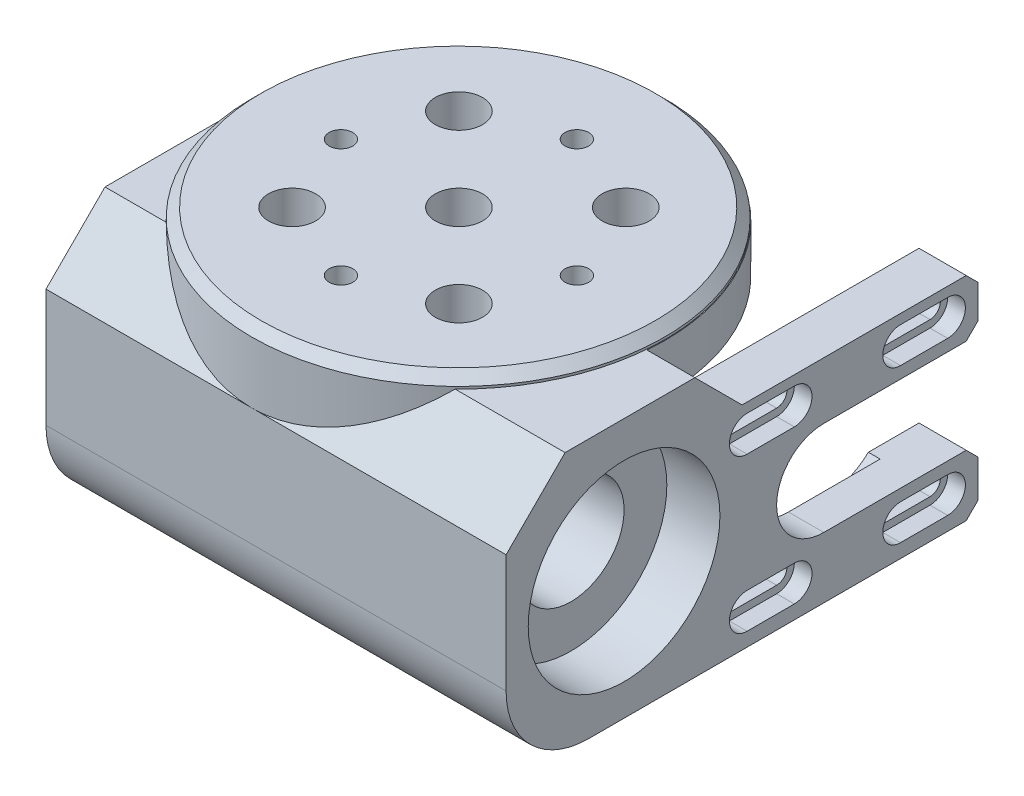
SolidWorks part; units mm, degrees
material "PLA Generic"
ref_plane "Front Plane" through (0, 0, 0) normal (0, 0, 1) x (1, 0, 0)
ref_plane "Top Plane" through (0, 0, 0) normal (0, 1, 0) x (1, 0, 0)
ref_plane "Right Plane" through (0, 0, 0) normal (1, 0, 0) x (0, 0, -1)
sketch "Sketch1" plane through (0, 0, 0) normal (0, 1, 0) x (1, 0, 0)
  circle A0 centre (0, 0) radius 4
  circle A1 centre (-0.1257, 0) radius 35
  dimension "D1" = 8
  dimension "D2" = 70
extrude "Boss-Extrude1" add sketch "Sketch1" along normal blind 2
chamfer "Chamfer1" distance 1.6 angle 45 1 edges at (-0.1257, 2, 35)
sketch "Sketch2" plane through (0, 0, 0) normal (0, -1, 0) x (1, 0, 0)
  line L3 (-35, 0) -> (-35, 35)
  line L4 (-35, 35) -> (35, 35)
  line L5 (35, 35) -> (35, 0)
  circle A2 centre (0, 0) radius 4
  arc A3 (-35, 0) -> (35, 0) centre (0, 0) ccw
  dimension "D1" = 70
  dimension "D2" = 8
extrude "Boss-Extrude2" add sketch "Sketch2" along normal blind 8
sketch "Sketch3" plane through (0, -8, 0) normal (0, -1, 0) x (1, 0, 0)
  line L0 (-35, 0) -> (-35, 35)
  line L1 (11.619, -3) -> (27, -3)
  line L2 (35, 35) -> (35, -45)
  line L3 (-35, 35) -> (35, 35)
  line L4 (-34.641, -5) -> (-10.9087, -5)
  line L5 (35, -45) -> (27, -45)
  line L6 (27, -45) -> (27, -3)
  circle A0 centre (0, 0) radius 4
  arc A1 (-10.9087, -5) -> (11.619, -3) centre (0, 0) ccw
  arc A2 (-35, 0) -> (-34.641, -5) centre (0, 0) ccw
  dimension "D1" = 12
  dimension "D2" = 40
  dimension "D3" = 8
  dimension "D4" = 80
  dimension "D5" = 38
extrude "Boss-Extrude3" add sketch "Sketch3" along normal blind 36
sketch "Sketch4" plane through (35, 0, 0) normal (1, 0, 0) x (0, 0, -1)
  line L6 (0, 0) -> (-35, 0)
  line L7 (-35, 0) -> (-35, -44)
  line L8 (-35, -44) -> (45, -44)
  line L9 (45, -44) -> (45, -8)
  line L10 (45, -8) -> (0, -8)
  line L11 (0, -8) -> (0, 0)
  line L12 (0, 0) -> (-35, 0)
  line L13 (-35, 0) -> (-35, -44)
  line L14 (-35, -44) -> (45, -44)
  line L15 (45, -44) -> (45, -8)
  line L16 (45, -8) -> (0, -8)
  line L17 (0, -8) -> (0, 0)
  dimension "D1" = 0
extrude "Boss-Extrude4" add sketch "Sketch4" along normal blind 8
sketch "Sketch5" plane through (27, 0, 0) normal (-1, 0, 0) x (0, 0, 1)
  line L5 (-3, -8) -> (-22.2711, -8)
  line L6 (-22.2711, -8) -> (-45, -8)
  line L7 (-45, -8) -> (-45, -44)
  line L8 (-45, -44) -> (-3, -44)
  line L9 (-3, -44) -> (-3, -8)
  line L10 (-3, -8) -> (-22.2711, -8)
  line L11 (-22.2711, -8) -> (-45, -8)
  line L12 (-45, -8) -> (-45, -44)
  line L13 (-45, -44) -> (-3, -44)
  line L14 (-3, -44) -> (-3, -8)
  dimension "D1" = 0
extrude "Cut-Extrude1" cut sketch "Sketch5" against normal blind 8
sketch "Sketch6" plane through (-35, 0, 0) normal (-1, 0, 0) x (0, 0, 1)
  line L0 (35, -44) -> (35, 0) construction
  line L1 (33.4, 2) -> (-33.4, 2) construction
  circle A0 centre (15, -22.4) radius 9
  dimension "D1" = 20
  dimension "D2" = 24.4
  dimension "D3" = 18
extrude "Cut-Extrude2" cut sketch "Sketch6" against normal through all
sketch "Sketch7" plane through (43, 0, 0) normal (1, 0, 0) x (0, 0, -1)
  circle A0 centre (-15, -22.4) radius 16.25
  dimension "D1" = 32.5
extrude "Cut-Extrude3" cut sketch "Sketch7" against normal blind 9
sketch "Sketch8" plane through (-35, 0, 0) normal (-1, 0, 0) x (0, 0, 1)
  circle A0 centre (15, -22.4) radius 16.25
  dimension "D1" = 32.5
extrude "Cut-Extrude4" cut sketch "Sketch8" against normal blind 9
chamfer "Chamfer2" distance 10 angle 45 2 edges at (-17.5629, 0, 35) (21.4371, 0, 35)
fillet "Fillet1" radius 14 2 edges at (4, -44, 35) (-22.7749, -44, -5)
fillet "Fillet2" radius 14 1 edges at (23.3095, -44, -3)
sketch "Sketch9" plane through (35, 0, 0) normal (-1, 0, 0) x (0, 0, 1)
  line L3 (-45, -8) -> (-45, -44) construction
  line L6 (-45, -44) -> (-45, -25.6549) construction
  line L7 (-45, -25.6549) -> (-12, -25.6549) construction
  line L8 (-12, -8) -> (-12, -44) construction
  line L11 (-45, -33.6549) -> (-45, -17.6549)
  line L12 (-22.8603, -17.6549) -> (-22.8603, -33.6549) construction
  line L13 (-45, -17.6549) -> (-18.8603, -17.6549)
  line L14 (-45, -33.6549) -> (-18.8603, -33.6549)
  arc A4 (-18.8603, -33.6549) -> (-18.8603, -17.6549) centre (-18.8603, -25.6549) ccw
  circle A5 centre (15, -22.4) radius 9 construction
  point P3 (-45, -8)
  point P13 (-22.8603, -25.6549)
  dimension "D1" = 4
  dimension "D4" = 16
  dimension "D2" = 16
  dimension "D3" = 38
extrude "Cut-Extrude5" cut sketch "Sketch9" against normal blind 9
sketch "Sketch10" plane through (35, 0, 0) normal (-1, 0, 0) x (0, 0, 1)
  line L29 (-45, -8) -> (-45, -44) construction
  line L30 (-22.8603, -12.6549) -> (-22.8603, -38.6549) construction
  line L31 (-18.8603, -17.6549) -> (-18.8603, -33.6549) construction
  line L32 (-18.8603, -33.6549) -> (-45, -17.6549) construction
  line L33 (-45, -17.6549) -> (-45, -33.6549) construction
  line L34 (-45, -33.6549) -> (-18.8603, -17.6549) construction
  line L35 (-18.8603, -17.6549) -> (-45, -17.6549) construction
  line L36 (-26.8603, -17.6549) -> (-18.8603, -33.6549) construction
  line L37 (-35.8603, -25.6549) -> (-9.8603, -25.6549) construction
  line L38 (-35.8603, -38.6549) -> (-35.8603, -12.6549) construction
  line L39 (-35.8603, -12.6549) -> (-9.8603, -12.6549) construction
  line L40 (-9.8603, -12.6549) -> (-9.8603, -38.6549) construction
  line L41 (-9.8603, -38.6549) -> (-35.8603, -38.6549) construction
  line L42 (-39.8603, -12.6549) -> (-31.8603, -12.6549) construction
  line L43 (-39.8603, -10.9049) -> (-31.8603, -10.9049)
  line L44 (-39.8603, -14.4049) -> (-31.8603, -14.4049)
  line L45 (-39.8603, -38.6549) -> (-31.8603, -38.6549) construction
  line L46 (-39.8603, -36.9049) -> (-31.8603, -36.9049)
  line L47 (-39.8603, -40.4049) -> (-31.8603, -40.4049)
  line L48 (-13.8603, -12.6549) -> (-5.8603, -12.6549) construction
  line L49 (-13.8603, -10.9049) -> (-5.8603, -10.9049)
  line L50 (-13.8603, -14.4049) -> (-5.8603, -14.4049)
  line L51 (-13.8603, -38.6549) -> (-5.8603, -38.6549) construction
  line L52 (-13.8603, -36.9049) -> (-5.8603, -36.9049)
  line L53 (-13.8603, -40.4049) -> (-5.8603, -40.4049)
  arc A8 (-39.8603, -10.9049) -> (-39.8603, -14.4049) centre (-39.8603, -12.6549) ccw
  arc A9 (-31.8603, -14.4049) -> (-31.8603, -10.9049) centre (-31.8603, -12.6549) ccw
  arc A10 (-39.8603, -36.9049) -> (-39.8603, -40.4049) centre (-39.8603, -38.6549) ccw
  arc A11 (-31.8603, -40.4049) -> (-31.8603, -36.9049) centre (-31.8603, -38.6549) ccw
  arc A12 (-13.8603, -10.9049) -> (-13.8603, -14.4049) centre (-13.8603, -12.6549) ccw
  arc A13 (-5.8603, -14.4049) -> (-5.8603, -10.9049) centre (-5.8603, -12.6549) ccw
  arc A14 (-13.8603, -36.9049) -> (-13.8603, -40.4049) centre (-13.8603, -38.6549) ccw
  arc A15 (-5.8603, -40.4049) -> (-5.8603, -36.9049) centre (-5.8603, -38.6549) ccw
  point P50 (-22.8603, -25.6549)
  point P53 (-22.8603, -25.6549)
  point P56 (-35.8603, -25.6549)
  point P60 (-35.8603, -12.6549)
  point P66 (-35.8603, -38.6549)
  point P73 (-9.8603, -12.6549)
  point P80 (-9.8603, -38.6549)
  dimension "D11" = 8
  dimension "D12" = 26
  dimension "D13" = 26
  dimension "D14" = 8
  dimension "D15" = 8
  dimension "D16" = 8
  dimension "D17" = 8
  dimension "D18" = 3.5
  dimension "D19" = 3.5
  dimension "D20" = 3.5
  dimension "D21" = 3.5
extrude "Cut-Extrude6" cut sketch "Sketch10" against normal blind 9
chamfer "Chamfer3" distance 2 angle 45 4 edges at (39, -17.6549, -45) (39, -8, -45) (39, -33.6549, -45) (39, -44, -45)
sketch "Sketch11" plane through (43, 0, 0) normal (1, 0, 0) x (0, 0, -1)
  line L0 (39.8603, -36.9049) -> (31.8603, -36.9049) construction
  line L1 (31.8603, -40.4049) -> (39.8603, -40.4049) construction
  line L2 (5.8603, -40.4049) -> (13.8603, -40.4049) construction
  line L3 (13.8603, -36.9049) -> (5.8603, -36.9049) construction
  line L4 (31.8603, -14.4049) -> (39.8603, -14.4049) construction
  line L5 (39.8603, -10.9049) -> (31.8603, -10.9049) construction
  line L6 (13.8603, -10.9049) -> (5.8603, -10.9049) construction
  line L7 (5.8603, -14.4049) -> (13.8603, -14.4049) construction
  line L8 (39.8603, -36.9049) -> (31.8603, -36.9049)
  line L9 (31.8603, -40.4049) -> (39.8603, -40.4049)
  line L10 (5.8603, -40.4049) -> (13.8603, -40.4049)
  line L11 (13.8603, -36.9049) -> (5.8603, -36.9049)
  line L12 (31.8603, -14.4049) -> (39.8603, -14.4049)
  line L13 (39.8603, -10.9049) -> (31.8603, -10.9049)
  line L14 (13.8603, -12.6549) -> (5.8603, -12.6549) construction
  line L15 (13.8603, -15.6549) -> (5.8603, -15.6549)
  line L16 (13.8603, -9.6549) -> (5.8603, -9.6549)
  line L17 (39.8603, -12.6549) -> (31.8603, -12.6549) construction
  line L18 (39.8603, -15.6549) -> (31.8603, -15.6549)
  line L19 (39.8603, -9.6549) -> (31.8603, -9.6549)
  line L20 (13.8603, -38.6549) -> (5.8603, -38.6549) construction
  line L21 (13.8603, -41.6549) -> (5.8603, -41.6549)
  line L22 (13.8603, -35.6549) -> (5.8603, -35.6549)
  line L23 (31.8603, -38.6549) -> (39.8603, -38.6549) construction
  line L24 (31.8603, -35.6549) -> (39.8603, -35.6549)
  line L25 (31.8603, -41.6549) -> (39.8603, -41.6549)
  line L42 (13.8603, -10.9049) -> (5.8603, -10.9049)
  line L43 (5.8603, -14.4049) -> (13.8603, -14.4049)
  arc A0 (39.8603, -40.4049) -> (39.8603, -36.9049) centre (39.8603, -38.6549) ccw construction
  arc A1 (31.8603, -36.9049) -> (31.8603, -40.4049) centre (31.8603, -38.6549) ccw construction
  arc A2 (13.8603, -15.6549) -> (13.8603, -9.6549) centre (13.8603, -12.6549) ccw
  arc A3 (5.8603, -9.6549) -> (5.8603, -15.6549) centre (5.8603, -12.6549) ccw
  arc A6 (5.8603, -36.9049) -> (5.8603, -40.4049) centre (5.8603, -38.6549) ccw construction
  arc A7 (13.8603, -40.4049) -> (13.8603, -36.9049) centre (13.8603, -38.6549) ccw construction
  arc A8 (39.8603, -14.4049) -> (39.8603, -10.9049) centre (39.8603, -12.6549) ccw construction
  arc A9 (31.8603, -10.9049) -> (31.8603, -14.4049) centre (31.8603, -12.6549) ccw construction
  arc A10 (5.8603, -10.9049) -> (5.8603, -14.4049) centre (5.8603, -12.6549) ccw construction
  arc A11 (13.8603, -14.4049) -> (13.8603, -10.9049) centre (13.8603, -12.6549) ccw construction
  arc A12 (39.8603, -40.4049) -> (39.8603, -36.9049) centre (39.8603, -38.6549) ccw
  arc A13 (31.8603, -36.9049) -> (31.8603, -40.4049) centre (31.8603, -38.6549) ccw
  arc A14 (5.8603, -36.9049) -> (5.8603, -40.4049) centre (5.8603, -38.6549) ccw
  arc A15 (13.8603, -40.4049) -> (13.8603, -36.9049) centre (13.8603, -38.6549) ccw
  arc A16 (39.8603, -14.4049) -> (39.8603, -10.9049) centre (39.8603, -12.6549) ccw
  arc A17 (31.8603, -10.9049) -> (31.8603, -14.4049) centre (31.8603, -12.6549) ccw
  arc A18 (5.8603, -10.9049) -> (5.8603, -14.4049) centre (5.8603, -12.6549) ccw
  arc A19 (13.8603, -14.4049) -> (13.8603, -10.9049) centre (13.8603, -12.6549) ccw
  arc A20 (39.8603, -15.6549) -> (39.8603, -9.6549) centre (39.8603, -12.6549) ccw
  arc A21 (31.8603, -9.6549) -> (31.8603, -15.6549) centre (31.8603, -12.6549) ccw
  arc A22 (13.8603, -41.6549) -> (13.8603, -35.6549) centre (13.8603, -38.6549) ccw
  arc A23 (5.8603, -35.6549) -> (5.8603, -41.6549) centre (5.8603, -38.6549) ccw
  arc A24 (31.8603, -35.6549) -> (31.8603, -41.6549) centre (31.8603, -38.6549) ccw
  arc A25 (39.8603, -41.6549) -> (39.8603, -35.6549) centre (39.8603, -38.6549) ccw
  point P0 (9.8603, -12.6549)
  point P5 (35.8603, -12.6549)
  point P15 (9.8603, -38.6549)
  point P26 (35.8603, -38.6549)
  dimension "D1" = 6
  dimension "D2" = 6
  dimension "D3" = 6
  dimension "D4" = 6
extrude "Cut-Extrude7" cut sketch "Sketch11" against normal blind 3
sketch "Sketch12" plane through (0, -8, 0) normal (0, -1, 0) x (1, 0, 0)
  line L1 (-3, -11.619) -> (-3, -34.8712)
  line L2 (3, -11.619) -> (3, -34.8712)
  arc A0 (-3, -11.619) -> (3, -11.619) centre (0, 0) ccw
  arc A1 (-3, -34.8712) -> (3, -34.8712) centre (0, 0) ccw
  point P7 (0, 0)
  dimension "D1" = 6
extrude "Boss-Extrude5" add sketch "Sketch12" along normal up to surface (36 mm away) up to face at (10.7864, -44, -3.2318)
chamfer "Chamfer4" distance 23 angle 57 1 edges at (0, -44, -35) first distance on face at (7.0601, -44, -8.2695)
sketch "Sketch13" plane through (0, 2, 0) normal (0, 1, 0) x (1, 0, 0)
  circle A0 centre (0, 20) radius 2
  circle A1 centre (20, 0) radius 2
  circle A2 centre (0, -20) radius 2
  circle A3 centre (-20, 0) radius 2
  point P12 (0, 0)
  dimension "D1" = 20
  dimension "D2" = 4
  dimension "D3" = 4
extrude "Cut-Extrude8" cut sketch "Sketch13" against normal blind 12
sketch "Sketch14" plane through (0, 2, 0) normal (0, 1, 0) x (1, 0, 0)
  line L0 (0, 0) -> (20.1067, 0) construction
  line L1 (0, 0) -> (14.1421, 14.1421) construction
  circle A0 centre (14.1421, 14.1421) radius 4
  circle A1 centre (14.1421, -14.1421) radius 4
  circle A2 centre (-14.1421, -14.1421) radius 4
  circle A3 centre (-14.1421, 14.1421) radius 4
  point P14 (0, 0)
  dimension "D3" = 8
  dimension "D1" = 45
  dimension "D2" = 20
  dimension "D4" = 4
extrude "Cut-Extrude9" cut sketch "Sketch14" against normal blind 7
sketch "Sketch15" plane through (0, -44, 0) normal (0, -1, 0) x (1, 0, 0)
  line L1 (0, 7.5056) -> (-6.5, 3.7528)
  line L2 (-6.5, 3.7528) -> (-6.5, -3.7528)
  line L3 (-6.5, -3.7528) -> (0, -7.5056)
  line L4 (0, -7.5056) -> (6.5, -3.7528)
  line L5 (6.5, -3.7528) -> (6.5, 3.7528)
  line L6 (6.5, 3.7528) -> (0, 7.5056)
  circle A0 centre (0, 0) radius 6.5 construction
  dimension "D1" = 13
extrude "Cut-Extrude10" cut sketch "Sketch15" against normal blind 15
sketch "Sketch16" plane through (0, 0, 0) normal (0, 0, -1) x (-1, 0, 0)
  line L0 (-35, -8) -> (-35, 0) construction
  line L1 (-43, -8) -> (-35, -8)
  line L2 (-43, -8) -> (-43, 0)
  line L3 (-43, 0) -> (-35, 0)
  line L4 (-35, -8) -> (-35, 0)
extrude "Boss-Extrude6" add sketch "Sketch16" along normal blind 5
chamfer "Chamfer5" distance 8 angle 45 1 edges at (39, 0, -5)
sketch "Sketch17" plane through (35, 0, 0) normal (-1, 0, 0) x (0, 0, 1)
  line L0 (-41.6103, -12.6549) -> (-41.6103, -38.6549) construction
  line L1 (-41.6103, -38.6549) -> (-4.1103, -38.6549) construction
  line L2 (-4.1103, -38.6549) -> (-4.152, -12.2755) construction
  line L3 (-4.152, -12.2755) -> (-41.6103, -12.6549) construction
  line L4 (-41.6103, -12.6549) -> (-4.1103, -38.6549) construction
  line L5 (-4.152, -12.2755) -> (-41.6103, -38.6549) construction
  line L6 (-26.8603, -25.6549) -> (-18.8603, -25.6549) construction
  line L7 (-26.8603, -14.6549) -> (-18.8603, -14.6549)
  line L8 (-26.8603, -36.6549) -> (-18.8603, -36.6549)
  arc A0 (-39.8603, -10.9049) -> (-39.8603, -14.4049) centre (-39.8603, -12.6549) ccw construction
  arc A1 (-39.8603, -36.9049) -> (-39.8603, -40.4049) centre (-39.8603, -38.6549) ccw construction
  arc A2 (-5.8603, -40.4049) -> (-5.8603, -36.9049) centre (-5.8603, -38.6549) ccw construction
  arc A3 (-5.8603, -14.4049) -> (-5.8603, -10.9049) centre (-5.8603, -12.6549) ccw construction
  arc A4 (-26.8603, -14.6549) -> (-26.8603, -36.6549) centre (-26.8603, -25.6549) ccw
  arc A5 (-18.8603, -36.6549) -> (-18.8603, -14.6549) centre (-18.8603, -25.6549) ccw
  point P18 (-22.8603, -25.6549)
  dimension "D1" = 8
  dimension "D2" = 22
extrude "Cut-Extrude11" cut sketch "Sketch17" against normal blind 2
ref_plane "Plane1" through (0, 0, 0) normal (1, 0, 0) x (0, 0, -1)
sketch "Sketch18" plane through (0, 0, 0) normal (1, 0, 0) x (0, 0, -1)
  point P0 (-15, -22.4)
